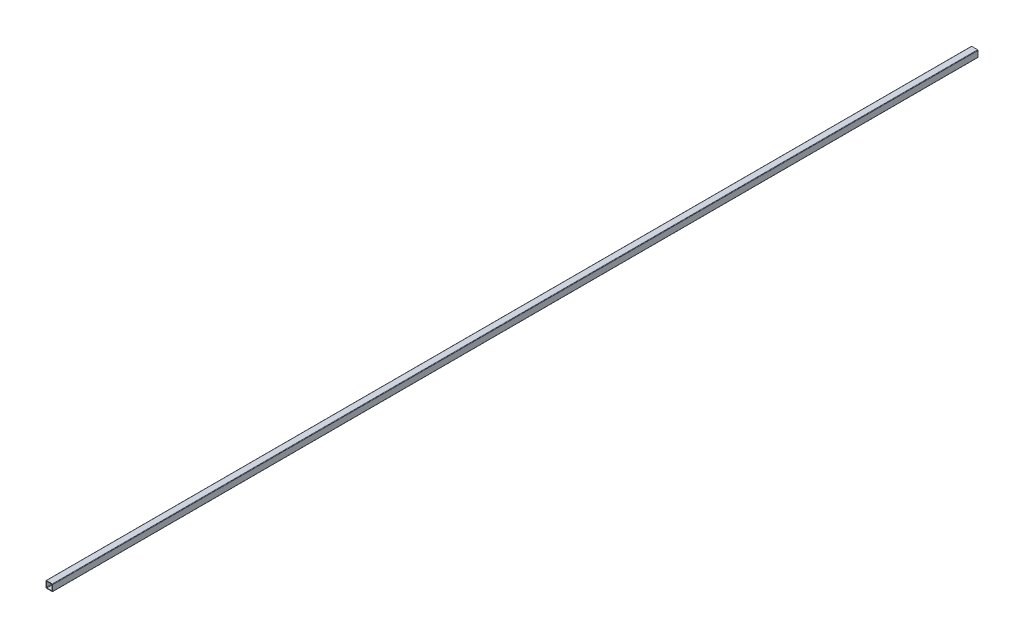
SolidWorks part; units mm, degrees
material "ASTM A500 Grade B Steel"
ref_plane "Front Plane" through (0, 0, 0) normal (0, 0, 1) x (1, 0, 0)
ref_plane "Top Plane" through (0, 0, 0) normal (0, 1, 0) x (1, 0, 0)
ref_plane "Right Plane" through (0, 0, 0) normal (1, 0, 0) x (0, 0, -1)
sketch "Sketch1" plane through (0, 0, 0) normal (0, 0, 1) x (1, 0, 0)
  line L0 (5.3086, -2.7686) -> (32.7914, -2.7686)
  line L1 (2.54, 0) -> (35.56, 0)
  line L2 (0, -2.54) -> (0, -35.56)
  line L3 (2.54, -38.1) -> (35.56, -38.1)
  line L4 (38.1, -2.54) -> (38.1, -35.56)
  line L5 (35.3314, -5.3086) -> (35.3314, -32.7914)
  line L6 (5.3086, -35.3314) -> (32.7914, -35.3314)
  line L7 (2.7686, -5.3086) -> (2.7686, -32.7914)
  line L8 (0, 0) -> (0, -38.1) construction
  line L9 (0, -38.1) -> (38.1, -38.1) construction
  line L10 (38.1, 0) -> (38.1, -38.1) construction
  line L11 (2.7686, -2.7686) -> (2.7686, -35.3314) construction
  line L12 (2.7686, -35.3314) -> (35.3314, -35.3314) construction
  line L13 (35.3314, -2.7686) -> (35.3314, -35.3314) construction
  line L14 (2.7686, -2.7686) -> (35.3314, -2.7686) construction
  line L15 (0, 0) -> (38.1, 0) construction
  arc A0 (0, -35.56) -> (2.54, -38.1) centre (2.54, -35.56) ccw
  arc A1 (38.1, -35.56) -> (35.56, -38.1) centre (35.56, -35.56) cw
  arc A2 (2.7686, -32.7914) -> (5.3086, -35.3314) centre (5.3086, -32.7914) ccw
  arc A3 (32.7914, -35.3314) -> (35.3314, -32.7914) centre (32.7914, -32.7914) ccw
  arc A4 (35.3314, -5.3086) -> (32.7914, -2.7686) centre (32.7914, -5.3086) ccw
  arc A5 (38.1, -2.54) -> (35.56, 0) centre (35.56, -2.54) ccw
  arc A6 (0, -2.54) -> (2.54, 0) centre (2.54, -2.54) cw
  arc A7 (5.3086, -2.7686) -> (2.7686, -5.3086) centre (5.3086, -5.3086) ccw
  point P12 (0, -38.1)
  dimension "D4" = 2.54
  dimension "D3" = 2.7686
extrude "Boss-Extrude1" add sketch "Sketch1" along normal blind 5243.8
sketch "Sketch2" plane through (0, -38.1, 0) normal (0, -1, 0) x (1, 0, 0)
  line L0 (19.05, 0) -> (19.05, 5243.8) construction
  line L1 (2.54, 0) -> (35.56, 0) construction
  line L2 (2.54, 5243.8) -> (35.56, 5243.8) construction
